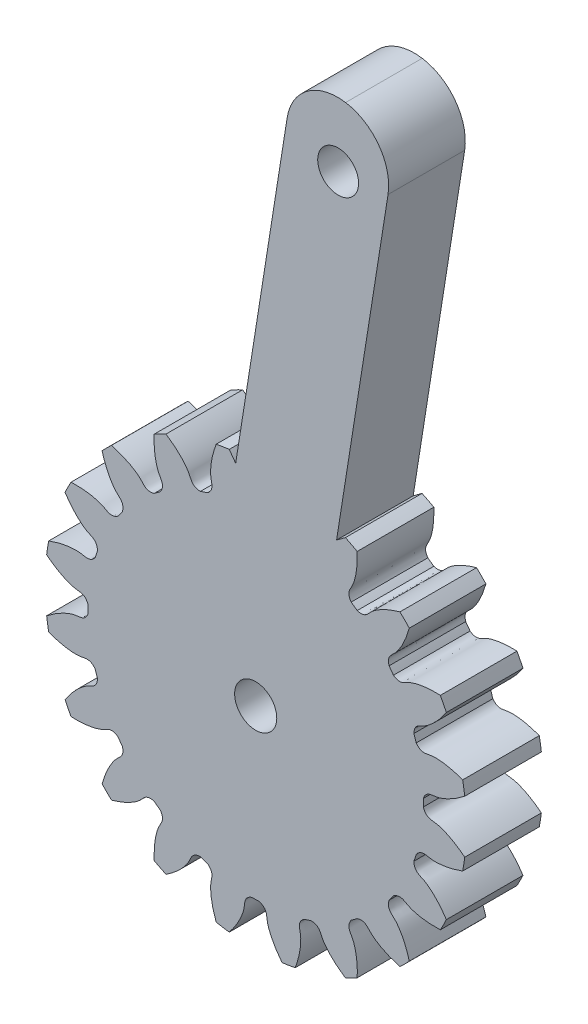
SolidWorks part; units mm, degrees
ref_plane "前视基准面" through (0, 0, 0) normal (0, 0, 1) x (1, 0, 0)
ref_plane "上视基准面" through (0, 0, 0) normal (0, 1, 0) x (1, 0, 0)
ref_plane "右视基准面" through (0, 0, 0) normal (1, 0, 0) x (0, 0, -1)
sketch "草图1" plane through (0, 0, 0) normal (0, 0, 1) x (1, 0, 0)
  circle A0 centre (0, 0) radius 16.5
extrude "凸台-拉伸1" add sketch "草图1" along normal blind 6
ref_axis "基准轴1" through (0, 0, -0.3) along (0, 0, 1)
sketch "草图2" plane through (0, 0, 0) normal (0, 0, 1) x (1, 0, 0)
  line L0 (0, 0) -> (0, 16.5) construction
  circle A0 centre (0, 0) radius 16.5 construction
  arc A1 (0.29, 13.1218) -> (-0.29, 13.1218) centre (0, 0) ccw
  arc A2 (4.7717, 18.7474) -> (-4.7717, 18.7474) centre (0, 0) ccw
  spline S0 degree 3 poles (0.29, 13.1218) (0.9168, 13.3402) (0.8356, 13.7807) (0.9193, 14.205) (0.9283, 14.2463) (0.9395, 14.293) (0.9529, 14.3448) (0.969, 14.4018) (0.9878, 14.4638) (1.0095, 14.5309) (1.0345, 14.6028) (1.0629, 14.6795) (1.0948, 14.7608) (1.1305, 14.8467) (1.1702, 14.9371) (1.2141, 15.0317) (1.2623, 15.1305) (1.315, 15.2334) (1.3725, 15.3401) (1.4349, 15.4506) (1.5023, 15.5646) (1.575, 15.6821) (1.653, 15.8029) (1.7366, 15.9267) (1.826, 16.0534) (1.9211, 16.1829) (2.0223, 16.3149) (2.1296, 16.4493) (2.2432, 16.5859) (2.3632, 16.7244) (2.4897, 16.8646) (2.6229, 17.0065) (2.7628, 17.1496) (2.9095, 17.2939) (3.0632, 17.4391) (3.224, 17.585) (3.3918, 17.7313) (3.567, 17.8779) (3.7493, 18.0245) (3.9391, 18.1709) (4.1363, 18.3167) (4.4122, 18.5125) (4.6259, 18.6545) (4.7717, 18.7474) knots 0 0 0 0 0.165916 0.170906 0.176664 0.183189 0.190482 0.198542 0.207371 0.216967 0.22733 0.238462 0.250361 0.263027 0.276462 0.290664 0.305634 0.321371 0.337876 0.355149 0.37319 0.391998 0.411574 0.431917 0.453028 0.474907 0.497554 0.520968 0.54515 0.570099 0.595817 0.622302 0.649554 0.677575 0.706363 0.735918 0.766242 0.797333 0.829191 0.861818 0.895212 0.929373 1 1 1 1
  spline S1 degree 3 poles (-0.29, 13.1218) (-0.9168, 13.3402) (-0.8356, 13.7807) (-0.9193, 14.205) (-0.9283, 14.2463) (-0.9395, 14.293) (-0.9529, 14.3448) (-0.969, 14.4018) (-0.9878, 14.4638) (-1.0095, 14.5309) (-1.0345, 14.6028) (-1.0629, 14.6795) (-1.0948, 14.7608) (-1.1305, 14.8467) (-1.1702, 14.9371) (-1.2141, 15.0317) (-1.2623, 15.1305) (-1.315, 15.2334) (-1.3725, 15.3401) (-1.4349, 15.4506) (-1.5023, 15.5646) (-1.575, 15.6821) (-1.653, 15.8029) (-1.7366, 15.9267) (-1.826, 16.0534) (-1.9211, 16.1829) (-2.0223, 16.3149) (-2.1296, 16.4493) (-2.2432, 16.5859) (-2.3632, 16.7244) (-2.4897, 16.8646) (-2.6229, 17.0065) (-2.7628, 17.1496) (-2.9095, 17.2939) (-3.0632, 17.4391) (-3.224, 17.585) (-3.3918, 17.7313) (-3.567, 17.8779) (-3.7493, 18.0245) (-3.9391, 18.1709) (-4.1363, 18.3167) (-4.4122, 18.5125) (-4.6259, 18.6545) (-4.7717, 18.7474) knots 0 0 0 0 0.165916 0.170906 0.176664 0.183189 0.190482 0.198542 0.207371 0.216967 0.22733 0.238462 0.250361 0.263027 0.276462 0.290664 0.305634 0.321371 0.337876 0.355149 0.37319 0.391998 0.411574 0.431917 0.453028 0.474907 0.497554 0.520968 0.54515 0.570099 0.595817 0.622302 0.649554 0.677575 0.706363 0.735918 0.766242 0.797333 0.829191 0.861818 0.895212 0.929373 1 1 1 1
extrude "切除-拉伸1" cut sketch "草图2" along normal through all
pattern_circular "阵列(圆周)1" count 20 every 18 about axis through (0, 0, -0.3) along (0, 0, 1) of "切除-拉伸1"
sketch "草图3" plane through (0, 0, 0) normal (0, 0, 1) x (1, 0, 0)
  circle A0 centre (0, 0) radius 15 construction
  dimension "Dn" = 30
sketch "草图5" plane through (0, 0, 0) normal (0, 0, -1) x (-1, 0, 0)
  circle A0 centre (0, 0) radius 10.75
  dimension "D1" = 21.5
extrude "切除-拉伸2" cut sketch "草图5" against normal blind 3
sketch "草图6" plane through (0, 0, 3) normal (0, 0, -1) x (-1, 0, 0)
  circle A0 centre (0, 0) radius 5
  dimension "D1" = 10
extrude "切除-拉伸3" cut sketch "草图6" against normal blind 3
sketch "草图7" plane through (0, 0, 3) normal (0, 0, -1) x (-1, 0, 0)
  line L0 (3.3, 0) -> (-3.3, 0) construction
  line L1 (0, 3.3) -> (0, -3.3) construction
  circle A0 centre (0, 7.25) radius 0.75
  circle A1 centre (7.25, 0) radius 0.75
  circle A2 centre (0, -7.25) radius 0.75
  circle A3 centre (-7.25, 0) radius 0.75
  dimension "D3" = 1.5
  dimension "D4" = 1.5
  dimension "D1" = 7.25
  dimension "D2" = 7.25
extrude "切除-拉伸4" cut sketch "草图7" against normal blind 3
sketch "草图8" plane through (0, 0, 0) normal (0, 0, -1) x (-1, 0, 0)
  circle A0 centre (0, 0) radius 10.75 construction
  circle A1 centre (0, 0) radius 10.75
extrude "凸台-拉伸2" add sketch "草图8" against normal blind 3
sketch "草图9" plane through (0, 0, 6) normal (0, 0, 1) x (1, 0, 0)
  line L0 (0, 0) -> (5.4772, 34.5817) construction
  line L1 (0, 0) -> (0, 33.0663) construction
  line L2 (-2.039, 12.6963) -> (5.8625, 11.4448)
  line L3 (5.8625, 11.4448) -> (11.7725, 48.7587)
  line L4 (11.7725, 48.7587) -> (3.871, 50.0102)
  line L5 (7.8217, 49.3844) -> (1.9118, 12.0705) construction
  line L6 (0, 0) -> (3.8964, -0.6171) construction
  line L7 (-2.039, 12.6963) -> (3.871, 50.0102)
  dimension "D1" = 9
  dimension "D2" = 4
  dimension "D3" = 50
extrude "凸台-拉伸3" add sketch "草图9" against normal up to surface (6 mm away) up to face at (0, 0, 0)
sketch "草图11" plane through (0, 0, 3) normal (0, 0, 1) x (1, 0, 0)
  circle A0 centre (0, 0) radius 1.65
  dimension "D1" = 3.3
extrude "切除-拉伸6" cut sketch "草图11" against normal blind 10
sketch "草图12" plane through (0, 0, 6) normal (0, 0, 1) x (1, 0, 0)
  circle A0 centre (0, 0) radius 8.7131
  circle A1 centre (0, 0) radius 1.65
extrude "凸台-拉伸4" add sketch "草图12" against normal up to surface (6 mm away) up to face at (1.65, 0, 0)
sketch "草图13" plane through (0, 0, 6) normal (0, 0, 1) x (1, 0, 0)
  line L0 (3.871, 50.0102) -> (11.7725, 48.7587)
  line L1 (11.7725, 48.7587) -> (10.9902, 43.8197)
  line L2 (6.3336, 14.4187) -> (11.7725, 48.7587) construction
  line L3 (10.9902, 43.8197) -> (3.0887, 45.0712)
  line L4 (3.871, 50.0102) -> (-1.568, 15.6701) construction
  line L5 (3.0887, 45.0712) -> (3.871, 50.0102)
  circle A0 centre (6.4568, 39.4754) radius 1.6
  dimension "D3" = 3.2
  dimension "D1" = 40
  dimension "D2" = 5
extrude "切除-拉伸7" cut sketch "草图13" against normal blind 10
fillet "圆角1" radius 4 2 edges at (10.9902, 43.8197, 3) (3.0887, 45.0712, 3)
